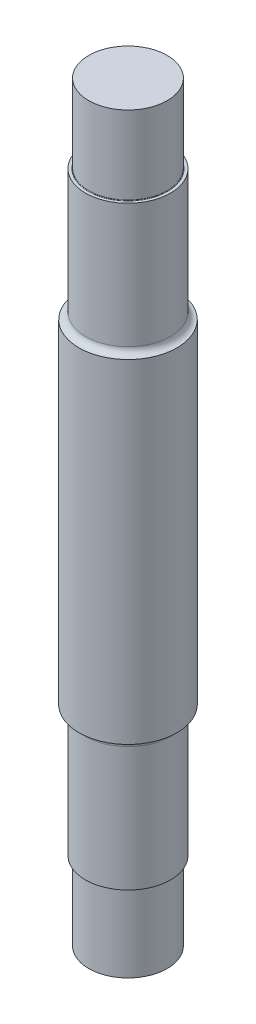
SolidWorks part; units mm, degrees
ref_plane "Alzado" through (0, 0, 0) normal (0, 0, 1) x (1, 0, 0)
ref_plane "Planta" through (0, 0, 0) normal (0, 1, 0) x (1, 0, 0)
ref_plane "Vista lateral" through (0, 0, 0) normal (1, 0, 0) x (0, 0, -1)
sketch "Croquis14" plane through (0, 0, 0) normal (0, 1, 0) x (1, 0, 0)
  circle A0 centre (0, 0) radius 30
extrude "Saliente-Extruir10" add sketch "Croquis14" along normal blind 60
sketch "Croquis15" plane through (0, 60, 0) normal (0, 1, 0) x (1, 0, 0)
  circle A0 centre (0, 0) radius 32.5
extrude "Saliente-Extruir11" add sketch "Croquis15" along normal blind 100
sketch "Croquis16" plane through (0, 160, 0) normal (0, 1, 0) x (1, 0, 0)
  circle A0 centre (0, 0) radius 37.5
  point P3 (31.6855, 15.7038)
extrude "Saliente-Extruir12" add sketch "Croquis16" along normal blind 255
sketch "Croquis17" plane through (0, 415, 0) normal (0, 1, 0) x (1, 0, 0)
  circle A0 centre (0, 0) radius 32.5
extrude "Saliente-Extruir13" add sketch "Croquis17" along normal blind 100
sketch "Croquis18" plane through (0, 515, 0) normal (0, 1, 0) x (1, 0, 0)
  circle A0 centre (0, 0) radius 30
extrude "Saliente-Extruir14" add sketch "Croquis18" along normal blind 60
ref_plane "Plano3" through (0, 0, -36) normal (0, 0, 1) x (1, 0, 0)
sketch "Croquis19" plane through (0, 0, -36) normal (0, 0, 1) x (1, 0, 0)
  line L0 (0, 608.1922) -> (0, 0) construction
  line L1 (-42.9288, 30) -> (48.2323, 30) construction
  line L2 (-30, 0) -> (30, 0) construction
  line L3 (-42.9288, 52) -> (48.2323, 52) construction
  line L4 (-30, 60) -> (30, 60) construction
  line L5 (0, 8) -> (0, 52) construction
  line L6 (-7.6318, 8) -> (-7.6318, 52)
  line L7 (7.6318, 8) -> (7.6318, 52)
  line L8 (-312.5428, 287.5) -> (324.842, 287.5) construction
  line L9 (0, 567) -> (0, 523) construction
  line L10 (-7.6318, 567) -> (-7.6318, 523)
  line L11 (7.6318, 567) -> (7.6318, 523)
  arc A0 (-7.6318, 8) -> (7.6318, 8) centre (0, 8) ccw
  arc A1 (7.6318, 52) -> (-7.6318, 52) centre (0, 52) ccw
  arc A2 (-7.6318, 567) -> (7.6318, 567) centre (0, 567) cw
  arc A3 (7.6318, 523) -> (-7.6318, 523) centre (0, 523) cw
  point P13 (0, 30)
  point P22 (0, 545)
  dimension "D1" = 30
  dimension "D2" = 8
  dimension "D3" = 287.5
extrude "Cortar-Extruir5" cut sketch "Croquis19" along normal blind 16
fillet "Redondeo9" radius 5 1 edges at (0, 415, 32.5)
fillet "Redondeo10" radius 0.4 1 edges at (0, 515, 30)
fillet "Redondeo11" radius 5 1 edges at (0, 160, 32.5)
fillet "Redondeo12" radius 0.4 1 edges at (0, 60, 30)
sketch "Croquis21" plane through (0, 0, 0) normal (0, 0, 1) x (1, 0, 0)
  line L0 (0, 668.1112) -> (0, -93.1112) construction
